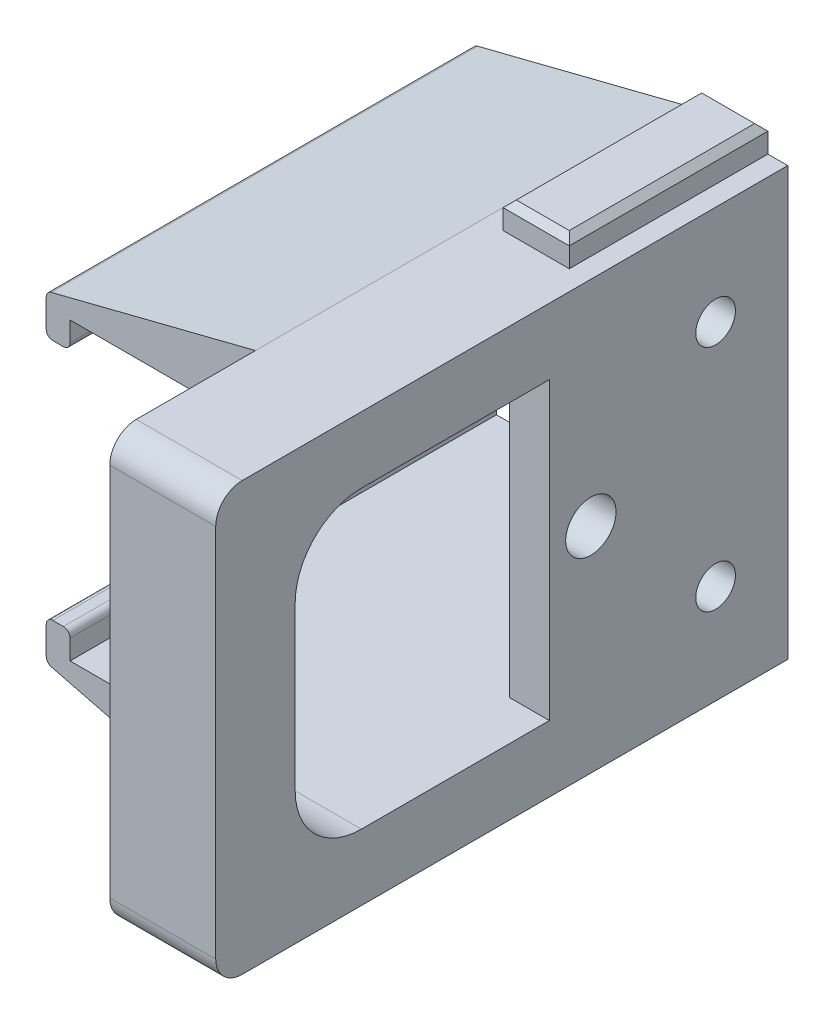
SolidWorks part; units mm, degrees
ref_plane "Front Plane" through (0, 0, 0) normal (0, 0, 1) x (1, 0, 0)
ref_plane "Top Plane" through (0, 0, 0) normal (0, 1, 0) x (1, 0, 0)
ref_plane "Right Plane" through (0, 0, 0) normal (1, 0, 0) x (0, 0, -1)
sketch "U" plane through (0, 0, 0) normal (1, 0, 0) x (0, 0, -1)
  line L0 (0, 22.3) -> (0, 27.3)
  line L1 (0, 0) -> (-32.2, 0)
  line L3 (0, 22.3) -> (-32.2, 22.3)
  line L4 (-37.2, 5) -> (-37.2, 17.3)
  line L5 (0, 27.3) -> (-41.2, 27.3)
  line L6 (-43.2, 25.3) -> (-43.2, -3)
  line L7 (-41.2, -5) -> (0, -5)
  line L8 (0, -5) -> (0, 0)
  arc A0 (-41.2, -5) -> (-43.2, -3) centre (-41.2, -3) cw
  arc A1 (-41.2, 27.3) -> (-43.2, 25.3) centre (-41.2, 25.3) ccw
  arc A2 (-37.2, 5) -> (-32.2, 0) centre (-32.2, 5) ccw
  arc A3 (-37.2, 17.3) -> (-32.2, 22.3) centre (-32.2, 17.3) cw
  point P15 (-37.2, 0)
  point P18 (-37.2, 22.3)
  dimension "D5" = 2
  dimension "D6" = 5
  dimension "D1" = 37.2
  dimension "D2" = 22.3
  dimension "D3" = 5
  dimension "D4" = 6
extrude "Boss-Extrude1" add sketch "U" against normal blind 5 and the other way blind 3
ref_plane "Plano1" through (0, 11.15, 0) normal (0, 1, 0) x (1, 0, 0)
sketch "Sketch2" plane through (0, 0, 0) normal (1, 0, 0) x (0, 0, -1)
  line L0 (0, 27.3) -> (-41.2, 27.3) construction
  line L1 (0, -5) -> (-18, -5)
  line L2 (0, -5) -> (0, 27.3)
  line L3 (0, 27.3) -> (-18, 27.3)
  line L4 (-18, -5) -> (-18, 27.3)
  circle A0 centre (-14.87, 11.15) radius 1.9
  dimension "D2" = 14.87
  dimension "D3" = 3.8
  dimension "D1" = 18
extrude "Boss-Extrude2" add sketch "Sketch2" along normal blind 3
sketch "AgujerosMotor" plane through (3, 0, 0) normal (1, 0, 0) x (0, 0, -1)
  line L0 (-5.45, 22.3) -> (-5.45, 0) construction
  line L1 (-18, 22.3) -> (0, 22.3) construction
  line L2 (-18, 22.3) -> (-18, 0) construction
  line L3 (-18, 0) -> (0, 0) construction
  line L4 (0, 22.3) -> (0, 0) construction
  line L5 (-5.45, 11.15) -> (0, 11.15) construction
  circle A0 centre (-5.45, 2.5) radius 1.5
  circle A1 centre (-5.45, 19.8) radius 1.5
  dimension "D2" = 3
  dimension "D1" = 5.45
  dimension "D3" = 2.5
extrude "Cut-Extrude1" cut sketch "AgujerosMotor" against normal up to next
sketch "Sketch5" plane through (-5, 0, 0) normal (-1, 0, 0) x (0, 0, 1)
  line L0 (32.2, 22.3) -> (0, 22.3) construction
  line L5 (0, 27.3) -> (32.2, 27.3)
  line L6 (0, 27.3) -> (0, 22.3)
  line L7 (0, 22.3) -> (32.2, 22.3)
  line L8 (32.2, 27.3) -> (32.2, 22.3)
  arc A0 (37.2, 17.3) -> (32.2, 22.3) centre (32.2, 17.3) ccw construction
extrude "Boss-Extrude3" add sketch "Sketch5" along normal blind 15.8
chamfer "Chaflán1" distance 15.8 distance2 4 1 edges at (-20.8, 27.3, 16.1) first distance on face at (-7.6, 27.3, 24.4667)
sketch "Croquis1" plane through (0, 22.3, 0) normal (0, -1, 0) x (1, 0, 0)
  line L0 (-20.8, 32.2) -> (-5, 32.2) construction
  line L1 (-20.8, 0) -> (-19, 0)
  line L2 (-20.8, 0) -> (-20.8, 32.2)
  line L3 (-20.8, 32.2) -> (-19, 32.2)
  line L4 (-19, 0) -> (-19, 32.2)
  dimension "D1" = 1.8
extrude "Saliente-Extruir1" add sketch "Croquis1" along normal blind 2
fillet "Redondeo2" radius 0.5 3 edges at (-20.8, 23.3, 16.1) (-20.8, 20.3, 16.1) (-19, 20.3, 16.1)
sketch "Croquis3" plane through (0, 27.3, 0) normal (0, 1, 0) x (1, 0, 0)
  line L1 (-3.5, -15) -> (1.5, -15)
  line L2 (-3.5, -15) -> (-3.5, 0)
  line L3 (-3.5, 0) -> (1.5, 0)
  line L4 (1.5, -15) -> (1.5, 0)
  line L5 (3, 0) -> (-5, 0) construction
  point P6 (-1, 0)
  point P7 (-1, 0)
  dimension "D1" = 15
  dimension "D2" = 5
extrude "Saliente-Extruir2" add sketch "Croquis3" along normal blind 2
chamfer "Chaflán2" distance 0.5 4 edges at (-1, 29.3, 0) (-3.5, 29.3, 7.5) (-1, 29.3, 15) (1.5, 29.3, 7.5)
mirror "Simetría11" about plane through (0, 11.15, 0) normal (0, 1, 0) of "Boss-Extrude3"
chamfer "Chaflán3" distance 4 distance2 15.8 1 edges at (-20.8, -5, 16.1) first distance on face at (-20.8, -2.5, 16.1)
mirror "Simetría14" about plane through (0, 11.15, 0) normal (0, 1, 0) of "Saliente-Extruir1"
mirror "Simetría15" about plane through (0, 11.15, 0) normal (0, 1, 0) of "Chaflán2", "Saliente-Extruir2"
fillet "Redondeo3" radius 0.5 3 edges at (-20.8, -1, 16.1) (-19, 2, 16.1) (-20.8, 2, 16.1)
